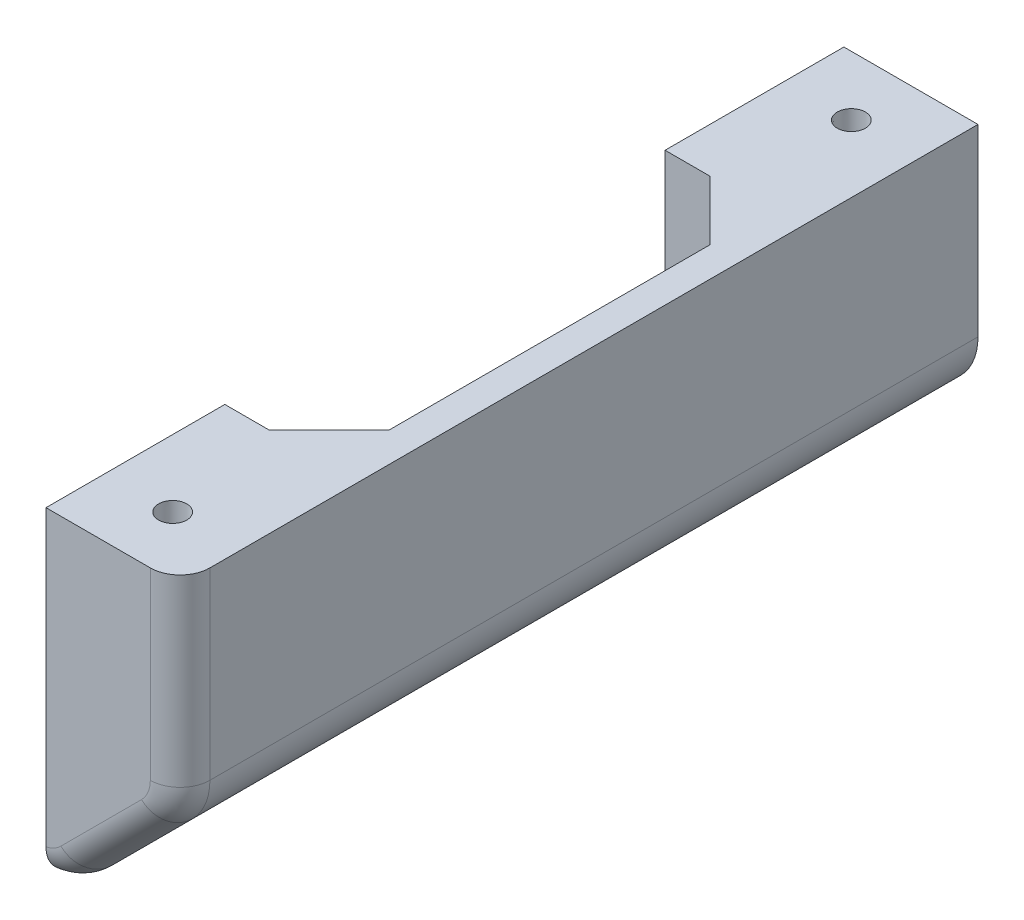
SolidWorks part; units mm, degrees
material "PET"
ref_plane "Front Plane" through (0, 0, 0) normal (0, 0, 1) x (1, 0, 0)
ref_plane "Top Plane" through (0, 0, 0) normal (0, 1, 0) x (1, 0, 0)
ref_plane "Right Plane" through (0, 0, 0) normal (1, 0, 0) x (0, 0, -1)
sketch "Sketch1" plane through (0, 0, 0) normal (0, 0, 1) x (1, 0, 0)
  line L0 (-202.7295, 69) -> (-202.7295, 24.55)
  line L2 (-202.7295, 24.55) -> (-227.2795, 0)
  line L3 (-227.2795, 0) -> (-231.3045, 0)
  line L4 (-231.3045, 0) -> (-231.3045, 69)
  line L5 (-231.3045, 69) -> (-202.7295, 69)
  line L6 (-4.0045, 69) -> (-244.0045, 69) construction
  line L7 (-16.7045, 0) -> (-231.3045, 0) construction
  line L8 (-231.3045, 12.7) -> (-231.3045, 69) construction
  dimension "D1" = 44.45
  dimension "D2" = 135
  dimension "D3" = 28.575
extrude "Boss-Extrude1" add sketch "Sketch1" along normal up to surface (170 mm away)
shell "Shell1" thickness 6.35 removed face at (-217.017, 69, 85) removed face at (-231.3045, 34.5, 85)
fillet "Fillet1" radius 12.7 2 edges at (-202.7295, 24.55, 85) (-227.2795, 0, 85)
fillet "Fillet2" radius 6.35 4 edges at (-202.7295, 49.4053, 170) (-203.6962, 24.9504, 170) (-215.0379, 12.2415, 170) (-227.1508, 1.1648, 170)
sketch "Sketch10" plane through (-231.3045, 0, 0) normal (-1, 0, 0) x (0, 0, 1)
  line L1 (6.35, 69) -> (38.1, 69)
  line L2 (6.35, 69) -> (6.35, 6.35)
  line L3 (6.35, 6.35) -> (38.1, 6.35)
  line L4 (38.1, 69) -> (38.1, 6.35)
  line L5 (0, 69) -> (0, 0) construction
  line L6 (85, 69) -> (85, 0) construction
  line L7 (163.65, 69) -> (6.35, 69) construction
  line L9 (163.65, 0) -> (0, 0) construction
  line L10 (131.9, 69) -> (131.9, 6.35)
  line L11 (163.65, 6.35) -> (131.9, 6.35)
  line L12 (163.65, 69) -> (163.65, 6.35)
  line L13 (163.65, 69) -> (131.9, 69)
  line L14 (163.65, 6.35) -> (6.35, 6.35) construction
  dimension "D1" = 38.1
extrude "Boss-Extrude2" add sketch "Sketch10" against normal up to next
hole_wizard "Hole1" positions "Sketch2" profile "Sketch3" legacy
sketch "Sketch2" plane through (0, 69, 0) normal (0, 1, 0) x (1, 0, 0)
  line L4 (-217.017, -170) -> (-217.017, 0) construction
  line L5 (-202.7295, 0) -> (-231.3045, 0) construction
  line L6 (-209.0795, -170) -> (-231.3045, -170) construction
  line L7 (-217.017, -85) -> (-202.7295, -85) construction
  line L8 (-202.7295, -163.65) -> (-202.7295, 0) construction
  point P14 (-217.017, -12.7)
  point P18 (-217.017, -157.3)
  dimension "D1" = 12.7
  dimension "D2" = 12.7
sketch "Sketch3" plane through (-217.017, 69, 157.3) normal (1, 0, 0) x (0, 0, 1)
  line L0 (0, 0) -> (0, 4.699)
  line L1 (0, 4.699) -> (2.8702, 4.699)
  line L2 (2.8702, 4.699) -> (2.9972, 0)
  line L3 (2.9972, 0) -> (0, 0)
  line L4 (0, 110) -> (0, -10) construction
  dimension "Minor Diameter" = 5.7404
  dimension "Depth" = 4.699
  dimension "Major Diameter" = 5.9944
hole_wizard "#8 Clearance Hole1" positions "Sketch4" profile "Sketch5" hole size "#8" standard "ANSI Inch"
sketch "Sketch4" plane through (0, 69, 0) normal (0, 1, 0) x (1, 0, 0)
  point P0 (-217.017, -157.3)
  point P3 (-217.017, -12.7)
sketch "Sketch5" plane through (-217.017, 69, 157.3) normal (1, 0, 0) x (0, 0, 1)
  line L0 (0, 0) -> (0, 20.5266)
  line L1 (0, 20.5266) -> (2.4574, 19.05)
  line L2 (2.4574, 19.05) -> (2.4574, 0)
  line L5 (2.4574, 0) -> (0, 0)
  line L10 (0, 20.5266) -> (-2.4575, 19.05) construction
  line L11 (0, -6.35) -> (0, 107.95) construction
  dimension "Hole Dia." = 4.9149
  dimension "Hole Depth" = 19.05
  dimension "Drill Angle" = 118
hole_wizard "Hole2" positions "Sketch6" profile "Sketch7" legacy
sketch "Sketch6" plane through (-231.3045, 0, 0) normal (-1, 0, 0) x (0, 0, 1)
  line L4 (141.425, 69) -> (141.425, 0) construction
  line L6 (163.65, 0) -> (0, 0) construction
  line L7 (19.05, 69) -> (19.05, 0) construction
  line L8 (38.1, 69) -> (0, 69) construction
  line L9 (170, 69) -> (131.9, 69) construction
  line L10 (170, 69) -> (170, 6.418) construction
  point P16 (141.425, 34.5)
  point P24 (19.05, 34.5)
  dimension "D1" = 28.575
sketch "Sketch7" plane through (-231.3045, 34.5, 19.05) normal (0, 1, 0) x (0, 0, 1)
  line L0 (0, 0) -> (0, 4.699)
  line L1 (0, 4.699) -> (2.8702, 4.699)
  line L2 (2.8702, 4.699) -> (2.9972, 0)
  line L3 (2.9972, 0) -> (0, 0)
  line L4 (0, 110) -> (0, -10) construction
  dimension "Minor Diameter" = 5.7404
  dimension "Depth" = 4.699
  dimension "Major Diameter" = 5.9944
hole_wizard "#8 Clearance Hole2" positions "Sketch8" profile "Sketch9" hole size "#8" standard "ANSI Inch"
sketch "Sketch8" plane through (-231.3045, 0, 0) normal (-1, 0, 0) x (0, 0, 1)
  point P0 (141.425, 34.5)
  point P4 (19.05, 34.5)
sketch "Sketch9" plane through (-231.3045, 34.5, 141.425) normal (0, 1, 0) x (0, 0, 1)
  line L0 (0, 0) -> (0, 20.5266)
  line L1 (0, 20.5266) -> (2.4574, 19.05)
  line L2 (2.4574, 19.05) -> (2.4574, 0)
  line L5 (2.4574, 0) -> (0, 0)
  line L10 (0, 20.5266) -> (-2.4574, 19.05) construction
  line L11 (0, -6.35) -> (0, 107.95) construction
  dimension "Hole Dia." = 4.9149
  dimension "Hole Depth" = 19.05
  dimension "Drill Angle" = 118
chamfer "Chamfer1" distance 12.7 angle 45 4 edges at (-219.4946, 16.7651, 131.9) (-209.0795, 48.0901, 131.9) (-219.4946, 16.7651, 38.1) (-209.0795, 48.0901, 38.1)
